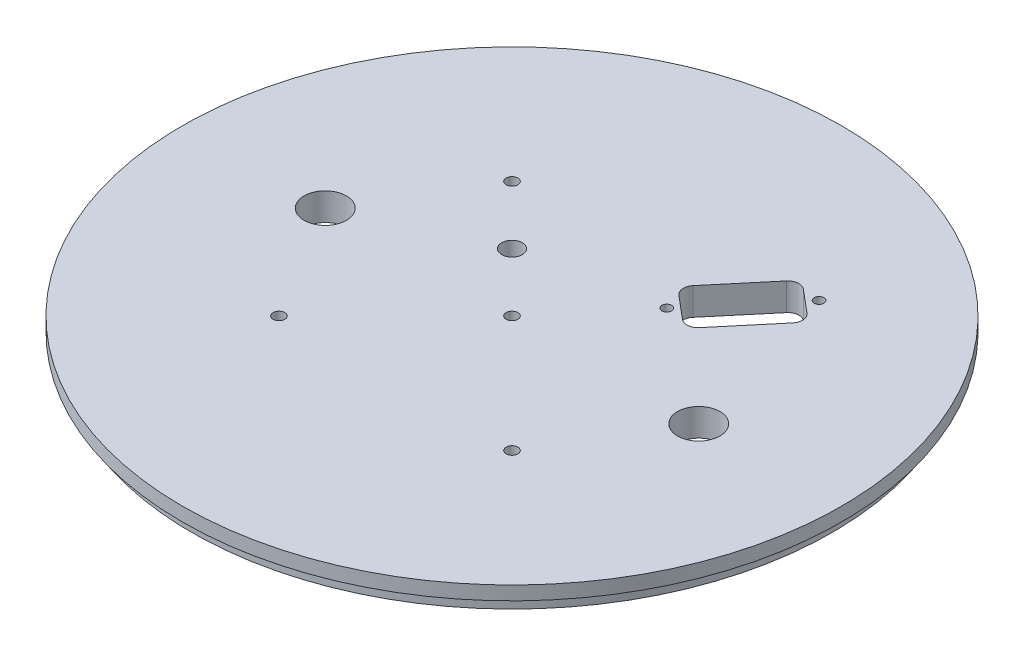
SolidWorks part; units mm, degrees
material "6061-T6 (SS)"
ref_plane "Front Plane" through (0, 0, 0) normal (0, 0, 1) x (1, 0, 0)
ref_plane "Top Plane" through (0, 0, 0) normal (0, 1, 0) x (1, 0, 0)
ref_plane "Right Plane" through (0, 0, 0) normal (1, 0, 0) x (0, 0, -1)
sketch "Sketch1" plane through (0, 0, 0) normal (0, 1, 0) x (1, 0, 0)
  line L0 (0, -76.2) -> (0, 76.2) construction
  line L1 (-76.2, 0) -> (76.2, 0) construction
  line L2 (-26.9408, 26.9408) -> (0, 0) construction
  line L3 (0, 56.7387) -> (0, 29.6936) construction
  line L4 (3.6407, 56.7387) -> (3.6407, 29.6936) construction
  line L5 (-3.6407, 56.7387) -> (-3.6407, 29.6936) construction
  line L6 (0, -56.7387) -> (0, -29.6936) construction
  line L7 (3.6407, -56.7387) -> (3.6407, -29.6936) construction
  line L8 (-3.6407, -56.7387) -> (-3.6407, -29.6936) construction
  line L9 (-53.8815, -53.8815) -> (54.3236, 54.3236) construction
  line L10 (-26.9408, -26.9408) -> (0, 0) construction
  circle A0 centre (0, 0) radius 76.2
  circle A1 centre (0, 0) radius 3.175 construction
  circle A2 centre (43.18, 0) radius 4.9022
  circle A3 centre (-43.18, 0) radius 4.9022
  circle A4 centre (-26.9408, 26.9408) radius 1.3589
  arc A6 (3.6407, 56.7387) -> (-3.6407, 56.7387) centre (0, 56.7387) ccw construction
  arc A7 (-3.6407, 29.6936) -> (3.6407, 29.6936) centre (0, 29.6936) ccw construction
  arc A8 (3.6407, -56.7387) -> (-3.6407, -56.7387) centre (0, -56.7387) cw construction
  arc A9 (-3.6407, -29.6936) -> (3.6407, -29.6936) centre (0, -29.6936) cw construction
  circle A10 centre (26.9408, -26.9408) radius 1.3589
  circle A11 centre (-13.4704, 13.4704) radius 2.3813
  circle A13 centre (-26.9408, -26.9408) radius 1.3589
  circle A14 centre (0, 0) radius 38.1 construction
  circle A15 centre (0, 0) radius 1.3589
  point P16 (0, 43.2162)
  point P19 (0, 0)
  point P26 (0, -43.2162)
  dimension "D1" = 152.4
  dimension "D2" = 6.35
  dimension "D3" = 9.8044
  dimension "D5" = 2.7178
  dimension "D8" = 4.7625
  dimension "D10" = 2.7178
  dimension "D12" = 2.7178
  dimension "D6" = 38.1
  dimension "D7" = 45
  dimension "D4" = 45
  dimension "D9" = 43.18
  dimension "D11" = 38.1
extrude "Boss-Extrude1" add sketch "Sketch1" along normal blind 6.35
sketch "Sketch2" plane through (0, 0, 0) normal (0, -1, 0) x (1, 0, 0)
  circle A0 centre (0, 0) radius 76.2
  circle A1 centre (0, 0) radius 74.041
  dimension "D1" = 152.4
  dimension "D2" = 148.082
extrude "Cut-Extrude1" cut sketch "Sketch2" against normal blind 3.175
sketch "Sketch3" plane through (0, 6.35, 0) normal (0, 1, 0) x (1, 0, 0)
  line L0 (0, 76.2) -> (0, -76.2) construction
  line L1 (-76.2, 0) -> (76.2, 0) construction
  line L2 (0, 34.798) -> (0, 13.97) construction
  line L3 (3.2385, 34.798) -> (3.2385, 13.97)
  line L4 (-3.2385, 34.798) -> (-3.2385, 13.97)
  line L5 (0, -34.798) -> (0, -13.97) construction
  line L6 (3.2385, -34.798) -> (3.2385, -13.97)
  line L7 (-3.2385, -34.798) -> (-3.2385, -13.97)
  circle A0 centre (0, 0) radius 76.2 construction
  arc A1 (3.2385, 34.798) -> (-3.2385, 34.798) centre (0, 34.798) ccw
  arc A2 (-3.2385, 13.97) -> (3.2385, 13.97) centre (0, 13.97) ccw
  arc A3 (3.2385, -34.798) -> (-3.2385, -34.798) centre (0, -34.798) cw
  arc A4 (-3.2385, -13.97) -> (3.2385, -13.97) centre (0, -13.97) cw
  point P7 (0, 13.97)
  point P8 (0, 34.798)
  point P12 (0, 24.384)
  point P20 (0, -24.384)
  point P25 (0, -34.798)
  point P26 (0, -13.97)
  dimension "D1" = 13.97
  dimension "D2" = 20.828
  dimension "D3" = 6.477
extrude "Cut-Extrude2" cut sketch "Sketch3" against normal blind 3.556 from offset 3.175 offset against normal yes
hole_wizard "Tap Drill for #4-40 Tap1" positions "Sketch5" profile "Sketch6" hole size "#4-40" standard "ANSI Inch" end condition through all
sketch "Sketch5" plane through (0, 6.35, 0) normal (0, 1, 0) x (1, 0, 0)
  line L0 (0, 0) -> (53.6567, 63.9455) construction
  line L2 (0, 0) -> (43.18, 0) construction
  point P0 (16.3268, 19.4575)
  point P2 (32.3965, 38.6086)
  dimension "D1" = 50
  dimension "D2" = 25
  dimension "D3" = 25.4
sketch "Sketch6" plane through (16.3268, 6.35, -19.4575) normal (1, 0, 0) x (0, 0, 1)
  line L0 (0, 0) -> (0, 6.35)
  line L1 (0, 6.35) -> (1.1303, 6.35)
  line L2 (1.1303, 6.35) -> (1.1303, 0)
  line L5 (1.1303, 0) -> (0, 0)
  line L11 (0, -6.35) -> (0, 107.95) construction
  dimension "Thru Hole Dia." = 2.2606
  dimension "Thru Hole Depth" = 6.35
sketch "Sketch4" plane through (0, 6.35, 0) normal (0, 1, 0) x (1, 0, 0)
  line L0 (15.1695, 23.4128) -> (20.423, 19.0046)
  line L1 (14.8564, 26.9913) -> (24.7219, 38.7485)
  line L2 (24.0014, 19.3177) -> (33.8669, 31.0749)
  line L3 (28.3003, 39.0616) -> (33.5538, 34.6533)
  line L4 (0, 0) -> (32.3965, 38.6086) construction
  circle A1 centre (16.3268, 19.4575) radius 1.1303 construction
  arc A2 (24.7219, 38.7485) -> (28.3003, 39.0616) centre (26.6676, 37.1158) cw
  arc A3 (33.8669, 31.0749) -> (33.5538, 34.6533) centre (31.9212, 32.7076) ccw
  arc A4 (20.423, 19.0046) -> (24.0014, 19.3177) centre (22.0557, 20.9503) ccw
  arc A5 (14.8564, 26.9913) -> (15.1695, 23.4128) centre (16.8021, 25.3586) ccw
  point P11 (17.7962, 21.2087)
  dimension "D4" = 2.54
  dimension "D1" = 2.286
  dimension "D2" = 2.286
  dimension "D3" = 11.938
extrude "Cut-Extrude3" cut sketch "Sketch4" against normal through all
equation "\"leadDist\"=1.5"
equation "\"Lead_Screw_Dist\" = 3.4in"
equation "\"D9@Sketch1\"=\"Lead_Screw_Dist\"/2"
equation "\"Lead_Screw_Diam\" = 0.386in"
equation "\"D3@Sketch1\"=\"Lead_Screw_Diam\""
equation "\"Bodytube_OD\" = 6.17in"
equation "\"Bodytube_ID\" = 5.998in"
equation "\"Motor_OD\" = 4in"
equation "\"Fwd_Tube_Length\" = 40in"
equation "\"Mid_Tube_Length\" = 1in"
equation "\"Aft_Section_Length\"= 39in"
equation "\"AB_Coupler_OD_Length\"= 1in"
equation "\"AB_Coupling_Section_Length\"= 0.375in"
equation "\"AB_Coupler_Length\"= \"AB_Coupler_OD_Length\" + \"AB_Coupling_Section_Length\" * 2"
equation "\"Cutout_Angle\" = 80"
equation "\"AB_Paddle_Height\" = 0.375in"
equation "\"AB_Coupler_Num_Screws\"= 6"
equation "\"Num_Cutouts\" = 3"
equation "\"AB_Coupler_OD\"= 6.17in"
equation "\"AB_Coupler_ID\"= 5.75in"
equation "\"AB_Coupler_Surface_Diameter\"= 5.998in"
equation "\"AB_Coupling_Screw_Diameter\"= 0.1065in"
equation "\"AB_Central_Bushing_Length\" = .75in"
equation "\"Lead_Screw_Length\" = (\"Mid_Coupler_Length\" + 2*0.375in + 2*0.5in)"
equation "\"Paddle_Pin_Offset\" = .25in"
equation "\"Paddle_Pin_Radius\" = 2.25in"
equation "\"SS_Paddle_Pin_Radius\" = 2.25*0.66in"
equation "\"Paddle_Gear_OD\" = 3.2in"
equation "\"Drive_Gear_OD\" = 1.7in"
equation "\"Fwd_BKHD_From_Top\" = 18in"
equation "\"Fin_Thickness\"= .118in"
equation "\"Guiderail_Cutout_Diameter\"= 1.5in"
equation "\"DB9_Hole_Dist\" = 25mm"
equation "\"Airbrakes_Wire_Hole_Dia\" = .25in"
equation "\"Airbrakes_Wire_Hole_Dist\" = 1.1in"
equation "\"Servo_Gear_Offset\" = 0.5in"
equation "\"Mid_Coupler_Length\" = 13in"
equation "\"D2@Sketch5\"=\"DB9_Hole_Dist\""
equation "\"DB9_Relief_Width\" = 0.47in"
equation "\"DB9_Relief_Hole_Offset\" = 0.09in"
equation "\"D1@Sketch4\"=\"DB9_Relief_Hole_Offset\""
equation "\"D2@Sketch4\"=\"DB9_Relief_Hole_Offset\""
equation "\"D3@Sketch4\"=\"DB9_Relief_Width\""
